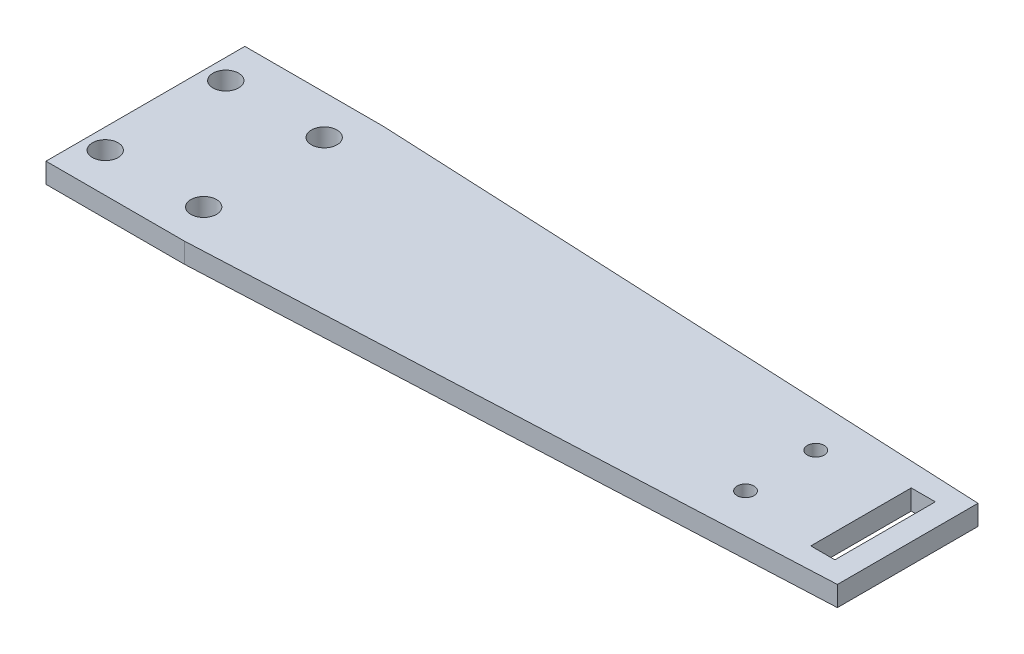
SolidWorks part; units mm, degrees
ref_plane "Front Plane" through (0, 0, 0) normal (0, 0, 1) x (1, 0, 0)
ref_plane "Top Plane" through (0, 0, 0) normal (0, 1, 0) x (1, 0, 0)
ref_plane "Right Plane" through (0, 0, 0) normal (1, 0, 0) x (0, 0, -1)
sketch "Sketch1" plane through (0, 0, 0) normal (0, 1, 0) x (1, 0, 0)
  line L1 (0, 0) -> (34.5, 0)
  line L2 (0, 0) -> (0, 49.5)
  line L3 (0, 49.5) -> (34.5, 49.5)
  line L4 (34.5, 0) -> (34.5, 49.5)
  dimension "D1" = 34.5
  dimension "D2" = 49.5
extrude "Boss-Extrude1" add sketch "Sketch1" along normal blind 5
sketch "Sketch2" plane through (0, 5, 0) normal (0, 1, 0) x (1, 0, 0)
  line L0 (34.5, 49.5) -> (0, 49.5) construction
  line L1 (0, 49.5) -> (0, 0) construction
  line L2 (17.25, 49.5) -> (17.25, 0) construction
  line L3 (0, 0) -> (34.5, 0) construction
  line L4 (0, 24.75) -> (17.25, 24.75) construction
  circle A0 centre (5, 39.75) radius 3.2
  circle A1 centre (5, 9.75) radius 3.2
  circle A2 centre (29.5, 9.75) radius 3.2
  circle A3 centre (29.5, 39.75) radius 3.2
  dimension "D1" = 6.4
  dimension "D3" = 5
  dimension "D2" = 9.75
extrude "Cut-Extrude1" cut sketch "Sketch2" against normal blind 5
sketch "Sketch3" plane through (0, 5, 0) normal (0, 1, 0) x (1, 0, 0)
  line L0 (17.25, 24.75) -> (181.75, 24.75) construction
  line L1 (189.75, 42.25) -> (34.5, 49.5)
  line L2 (189.75, 7.25) -> (34.5, 0)
  line L3 (189.75, 42.25) -> (189.75, 7.25)
  line L4 (171.0535, 14.3856) -> (89.0949, 10.5582)
  line L6 (171.0535, 35.1144) -> (89.0949, 38.9418)
  line L7 (34.5, 49.5) -> (34.5, 41.4913)
  line L8 (34.5, 0) -> (34.5, 49.5) construction
  line L9 (181.75, 34.6149) -> (34.1268, 41.5087) construction
  line L10 (34.5, 0) -> (34.5, 8.0087)
  line L11 (181.75, 14.8851) -> (34.1268, 7.9913) construction
  line L12 (84.0949, 39.1753) -> (84.0949, 10.3247)
  line L13 (89.0949, 38.9418) -> (89.0949, 10.5582)
  line L14 (89.0949, 39.1753) -> (89.0949, 10.3247) construction
  line L16 (0, 49.5) -> (0, 0) construction
  line L17 (0, 0) -> (34.5, 0) construction
  line L18 (84.0949, 39.1753) -> (34.5, 41.4913)
  line L19 (84.0949, 10.3247) -> (34.5, 8.0087)
  line L20 (171.0535, 35.1144) -> (171.0535, 14.3856)
  line L21 (181.75, 34.6149) -> (181.75, 14.8851) construction
  line L22 (178.13, 37.25) -> (184.13, 37.25)
  line L23 (178.13, 37.25) -> (178.13, 12.25)
  line L24 (178.13, 12.25) -> (184.13, 12.25)
  line L25 (184.13, 37.25) -> (184.13, 12.25)
  dimension "D1" = 17.5
  dimension "D4" = 17.25
  dimension "D5" = 24.75
  dimension "D6" = 17.5
  dimension "D7" = 172.5
  dimension "D8" = 25
  dimension "D9" = 12.5
  dimension "D10" = 6
  dimension "D11" = 5.62
  dimension "D2" = 8
  dimension "D3" = 5
extrude "Boss-Extrude2" add sketch "Sketch3" against normal blind 5
sketch "Sketch5" [suppressed] plane through (0, 5, 0) normal (0, 1, 0) x (1, 0, 0)
  line L0 (163.183, 43.1642) -> (163.183, 6.3358)
  line L1 (181.75, 42.25) -> (34.5, 49.5) construction
  line L2 (34.5, 0) -> (181.75, 7.25) construction
  line L3 (163.183, 6.3358) -> (181.75, 7.25)
  line L4 (181.75, 7.25) -> (181.75, 42.25)
  line L5 (181.75, 42.25) -> (163.183, 43.1642)
fillet "Fillet1" radius 10 6 edges at (89.0949, 2.5, -10.5582) (89.0949, 2.5, -38.9418) (84.0949, 2.5, -10.3247) (84.0949, 2.5, -39.1753) (34.5, 2.5, -41.4913) (34.5, 2.5, -8.0087)
fillet "Fillet2" radius 5 2 edges at (171.0535, 2.5, -14.3856) (171.0535, 2.5, -35.1144)
sketch "Sketch6" plane through (0, 5, 0) normal (0, 1, 0) x (1, 0, 0)
  line L4 (99.5614, 11.047) -> (166.2867, 14.163)
  line L5 (89.0949, 28.4639) -> (89.0949, 21.0361)
  line L6 (166.2867, 35.337) -> (99.5614, 38.453)
  line L7 (171.0535, 19.1576) -> (171.0535, 30.3424)
  line L8 (99.5614, 11.047) -> (166.2867, 14.163)
  line L9 (89.0949, 28.4639) -> (89.0949, 21.0361)
  line L10 (166.2867, 35.337) -> (99.5614, 38.453)
  line L11 (171.0535, 19.1576) -> (171.0535, 30.3424)
  line L12 (84.0949, 19.8687) -> (84.0949, 29.6313)
  line L13 (44.9665, 8.4975) -> (74.5614, 9.8795)
  line L14 (34.5, 31.0134) -> (34.5, 18.4866)
  line L15 (74.5614, 39.6205) -> (44.9665, 41.0025)
  line L16 (84.0949, 19.8687) -> (84.0949, 29.6313)
  line L17 (44.9665, 8.4975) -> (74.5614, 9.8795)
  line L18 (34.5, 31.0134) -> (34.5, 18.4866)
  line L19 (74.5614, 39.6205) -> (44.9665, 41.0025)
  arc A4 (89.0949, 21.0361) -> (99.5614, 11.047) centre (99.0949, 21.0361) ccw
  arc A5 (99.5614, 38.453) -> (89.0949, 28.4639) centre (99.0949, 28.4639) ccw
  arc A6 (171.0535, 30.3424) -> (166.2867, 35.337) centre (166.0535, 30.3424) ccw
  arc A7 (166.2867, 14.163) -> (171.0535, 19.1576) centre (166.0535, 19.1576) ccw
  arc A8 (89.0949, 21.0361) -> (99.5614, 11.047) centre (99.0949, 21.0361) ccw
  arc A9 (99.5614, 38.453) -> (89.0949, 28.4639) centre (99.0949, 28.4639) ccw
  arc A10 (171.0535, 30.3424) -> (166.2867, 35.337) centre (166.0535, 30.3424) ccw
  arc A11 (166.2867, 14.163) -> (171.0535, 19.1576) centre (166.0535, 19.1576) ccw
  arc A12 (74.5614, 9.8795) -> (84.0949, 19.8687) centre (74.0949, 19.8687) ccw
  arc A13 (34.5, 18.4866) -> (44.9665, 8.4975) centre (44.5, 18.4866) ccw
  arc A14 (44.9665, 41.0025) -> (34.5, 31.0134) centre (44.5, 31.0134) ccw
  arc A15 (84.0949, 29.6313) -> (74.5614, 39.6205) centre (74.0949, 29.6313) ccw
  arc A16 (74.5614, 9.8795) -> (84.0949, 19.8687) centre (74.0949, 19.8687) ccw
  arc A17 (34.5, 18.4866) -> (44.9665, 8.4975) centre (44.5, 18.4866) ccw
  arc A18 (44.9665, 41.0025) -> (34.5, 31.0134) centre (44.5, 31.0134) ccw
  arc A19 (84.0949, 29.6313) -> (74.5614, 39.6205) centre (74.0949, 29.6313) ccw
  dimension "D1" = 0
  dimension "D2" = 0
extrude "Boss-Extrude3" add sketch "Sketch6" against normal up to surface (5 mm away) up to face at (59.4966, 0, -24.75)
sketch "Sketch7" plane through (0, 5, 0) normal (0, 1, 0) x (1, 0, 0)
  line L0 (178.13, 24.75) -> (158.13, 24.75) construction
  line L1 (178.13, 37.25) -> (178.13, 12.25) construction
  line L2 (158.13, 16) -> (158.13, 33.5) construction
  circle A0 centre (158.13, 33.5) radius 2.1
  circle A1 centre (158.13, 16) radius 2.1
  point P7 (158.13, 24.75)
  dimension "D3" = 4.2
  dimension "D4" = 4.2
  dimension "D1" = 20
  dimension "D2" = 17.5
extrude "Cut-Extrude2" cut sketch "Sketch7" against normal through all
